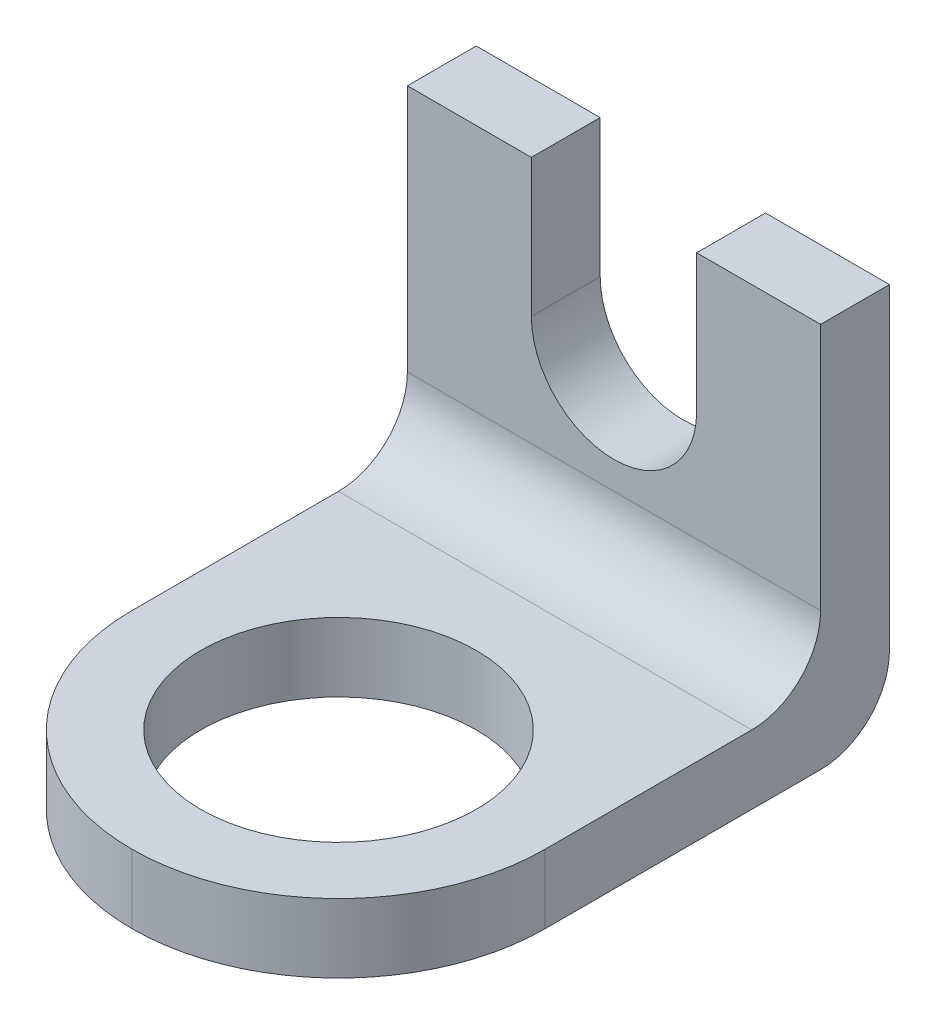
SolidWorks part; units mm, degrees
ref_plane "Спереди" through (0, 0, 0) normal (0, 0, 1) x (1, 0, 0)
ref_plane "Сверху" through (0, 0, 0) normal (0, 1, 0) x (1, 0, 0)
ref_plane "Справа" through (0, 0, 0) normal (1, 0, 0) x (0, 0, -1)
sketch "Эскиз1" plane through (0, 0, 0) normal (0, 0, 1) x (1, 0, 0)
  line L1 (-15, -14) -> (15, -14)
  line L2 (-15, -14) -> (-15, 14)
  line L3 (-15, 14) -> (15, 14)
  line L4 (15, -14) -> (15, 14)
  line L5 (-15, -14) -> (15, 14) construction
  line L6 (-15, 14) -> (15, -14) construction
  point P0 (0, 0)
  dimension "D1" = 30
  dimension "D2" = 28
extrude "Бобышка-Вытянуть1" add sketch "Эскиз1" along normal blind 5
sketch "Эскиз2" plane through (0, 0, 5) normal (0, 0, 1) x (1, 0, 0)
  line L0 (15, 14) -> (-15, 14) construction
  line L1 (-6, 14) -> (6, 14)
  line L2 (-6, 14) -> (-6, 4)
  line L3 (6, 14) -> (6, 4)
  arc A0 (-6, 4) -> (6, 4) centre (0, 4) ccw
  point P0 (-6, 14)
  point P1 (6, 14)
  dimension "D1" = 9
  dimension "D2" = 9
  dimension "D3" = 10
  dimension "D4" = 10
extrude "Вырез-Вытянуть1" cut sketch "Эскиз2" against normal through all
sketch "Эскиз3" plane through (0, 0, 5) normal (0, 0, 1) x (1, 0, 0)
  line L0 (-15, -14) -> (-15, -9)
  line L1 (-15, 14) -> (-15, -14) construction
  line L2 (-15, -9) -> (15, -9)
  line L3 (15, -14) -> (15, 14) construction
  line L4 (15, -9) -> (15, -14)
  line L5 (15, -14) -> (-15, -14)
  dimension "D1" = 5
extrude "Бобышка-Вытянуть2" add sketch "Эскиз3" along normal blind 35
fillet "Скругление1" radius 5 1 edges at (0, -14, 0) type face fillet first side face at (0, -14, 20) second side face at (0, 3.75, 0)
fillet "Скругление2" radius 15 1 edges at (15, -11.5, 40) type face fillet first side face at (15, -4.0051, 13.4235) second side face at (0, -11.5, 40)
fillet "Скругление3" radius 15 1 edges at (-15, -11.5, 40) type face fillet first side face at (-15, -4.0051, 13.4235) second side face at (-7.5, -11.5, 40)
sketch "Эскиз4" plane through (0, -9, 0) normal (0, 1, 0) x (1, 0, 0)
  line L0 (0, -40) -> (0, -25)
  circle A0 centre (0, -25) radius 10
  dimension "D2" = 20
  dimension "D1" = 15
extrude "Вырез-Вытянуть2" cut sketch "Эскиз4" along direction (0, -1, 0) on the side against the normal through all contours A0 region at (6.8711, -9, 31.8711)
fillet "Скругление5" radius 5 1 edges at (0, -9, 5)
